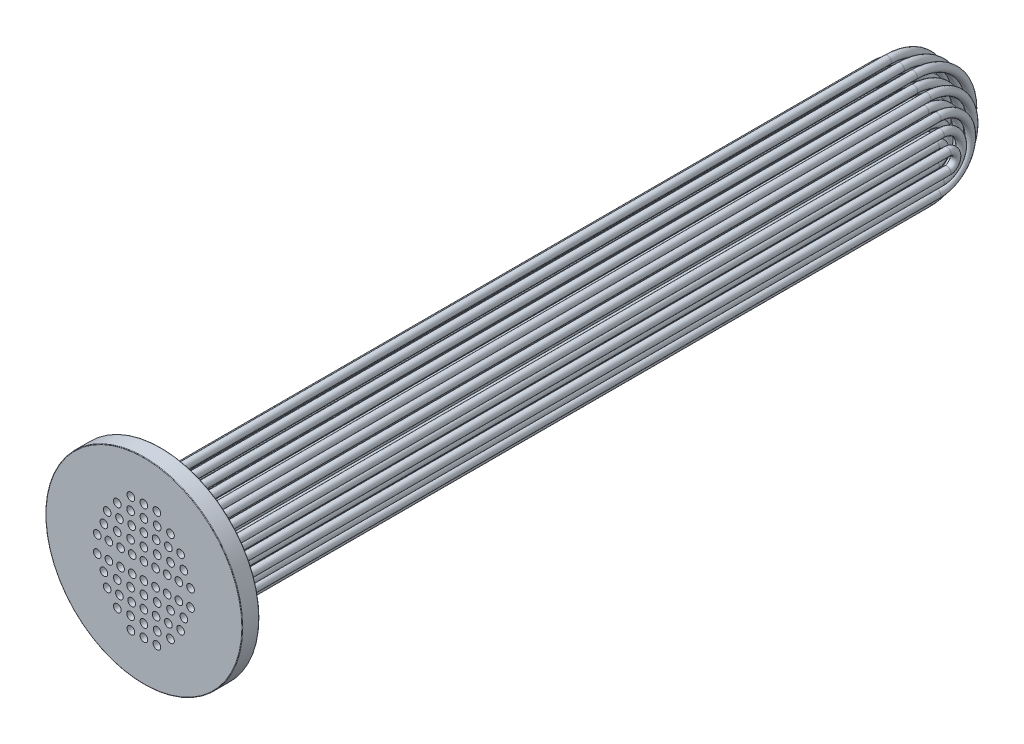
SolidWorks part; units mm, degrees
material "Copper"
ref_plane "Front Plane" through (0, 0, 0) normal (0, 0, 1) x (1, 0, 0)
ref_plane "Top Plane" through (0, 0, 0) normal (0, 1, 0) x (1, 0, 0)
ref_plane "Right Plane" through (0, 0, 0) normal (1, 0, 0) x (0, 0, -1)
ref_axis "Axis1" through (0, 0, -1.27) along (0, 0, 1)
ref_plane "Hub End Plane" through (0, 0, 88.9) normal (0, 0, 1) x (1, 0, 0)
sketch "Sketch1" plane through (0, 0, 0) normal (0, 0, 1) x (1, 0, 0)
  line L0 (0, 314.325) -> (0, 0) construction
  line L1 (41.0276, 311.6359) -> (0, 0) construction
  circle A1 centre (0, 0) radius 295.275
  circle A2 centre (0, 0) radius 314.325 construction
  circle A3 centre (41.0276, 311.6359) radius 17.4625 construction
  dimension "FlangeOD" = 590.55
  dimension "BoltHoleDia" = 34.925
  dimension "BoltCircle" = 628.65
  dimension "HoleOffsetAngle" = 7.5
extrude "Boss-Extrude1" add sketch "Sketch1" along normal blind 50.8
sketch "Sketch7" plane through (0, 0, 0) normal (0, 0, 1) x (1, 0, 0)
  circle A0 centre (0, 0) radius 230.886
  dimension "ID" = 461.772
fillet "Fillet2" radius 1.5875 2 edges at (295.275, 0, 50.8) (295.275, 0, 0)
ref_plane "lug mating plane" through (0, 0, 25.4) normal (0, 0, 1) x (1, 0, 0)
sketch "Sketch8" plane through (0, 0, 50.8) normal (0, 0, 1) x (1, 0, 0)
  line L0 (0, -211.4829) -> (0, 211.4829) construction
  line L1 (-293.6875, 0) -> (293.6875, 0) construction
  line L2 (0, 25) -> (35, 25) construction
  line L3 (0, 25) -> (-35, 25) construction
  line L4 (0, -25) -> (-35, -25) construction
  line L5 (0, -25) -> (35, -25) construction
  circle A1 centre (0, 25) radius 11.5
  circle A2 centre (0, 0) radius 293.6875 construction
  circle A3 centre (35, 25) radius 11.5
  circle A4 centre (70, 25) radius 11.5
  circle A5 centre (105, 25) radius 11.5
  circle A6 centre (140, 25) radius 11.5
  circle A9 centre (-35, 25) radius 11.5
  circle A10 centre (-70, 25) radius 11.5
  circle A11 centre (-105, 25) radius 11.5
  circle A12 centre (-140, 25) radius 11.5
  circle A15 centre (0, 62.2) radius 11.5
  circle A16 centre (0, 99.4) radius 11.5
  circle A17 centre (0, 136.6) radius 11.5
  circle A18 centre (0, 173.8) radius 11.5
  circle A20 centre (40, 62.2) radius 11.5
  circle A21 centre (80, 62.2) radius 11.5
  circle A22 centre (120, 62.2) radius 11.5
  circle A25 centre (-40, 62.2) radius 11.5
  circle A26 centre (-80, 62.2) radius 11.5
  circle A27 centre (-120, 62.2) radius 11.5
  circle A30 centre (36.7, 99.4) radius 11.5
  circle A31 centre (73.4, 99.4) radius 11.5
  circle A32 centre (110.1, 99.4) radius 11.5
  circle A35 centre (-36.7, 99.4) radius 11.5
  circle A36 centre (-73.4, 99.4) radius 11.5
  circle A37 centre (-110.1, 99.4) radius 11.5
  circle A40 centre (39.9, 136.6) radius 11.5
  circle A41 centre (79.8, 136.6) radius 11.5
  circle A44 centre (-39.9, 136.6) radius 11.5
  circle A45 centre (-79.8, 136.6) radius 11.5
  circle A48 centre (39, 173.8) radius 11.5
  circle A61 centre (-140, -25) radius 11.5
  circle A62 centre (-105, -25) radius 11.5
  circle A63 centre (-70, -25) radius 11.5
  circle A64 centre (-35, -25) radius 11.5
  circle A67 centre (140, -25) radius 11.5
  circle A68 centre (105, -25) radius 11.5
  circle A69 centre (70, -25) radius 11.5
  circle A70 centre (35, -25) radius 11.5
  circle A71 centre (0, -25) radius 11.5
  circle A73 centre (-110.1, -99.4) radius 11.5
  circle A74 centre (-73.4, -99.4) radius 11.5
  circle A75 centre (-36.7, -99.4) radius 11.5
  circle A78 centre (110.1, -99.4) radius 11.5
  circle A79 centre (73.4, -99.4) radius 11.5
  circle A80 centre (36.7, -99.4) radius 11.5
  circle A82 centre (-120, -62.2) radius 11.5
  circle A83 centre (-80, -62.2) radius 11.5
  circle A84 centre (-40, -62.2) radius 11.5
  circle A86 centre (120, -62.2) radius 11.5
  circle A87 centre (80, -62.2) radius 11.5
  circle A88 centre (40, -62.2) radius 11.5
  circle A89 centre (0, -99.4) radius 11.5
  circle A90 centre (0, -62.2) radius 11.5
  circle A95 centre (-39, -173.8) radius 11.5
  circle A98 centre (39, -173.8) radius 11.5
  circle A101 centre (-79.8, -136.6) radius 11.5
  circle A102 centre (-39.9, -136.6) radius 11.5
  circle A105 centre (79.8, -136.6) radius 11.5
  circle A106 centre (39.9, -136.6) radius 11.5
  circle A108 centre (0, -173.8) radius 11.5
  circle A109 centre (0, -136.6) radius 11.5
  circle A110 centre (0, 0) radius 173.8 construction
  circle A111 centre (117, 173.8) radius 11.5 [skipped]
  circle A112 centre (159.6, 136.6) radius 11.5 [skipped]
  circle A113 centre (183.5, 99.4) radius 11.5 [skipped]
  circle A114 centre (200, 62.2) radius 11.5 [skipped]
  circle A115 centre (210, 25) radius 11.5 [skipped]
  circle A116 centre (119.7, 136.6) radius 11.5 [skipped]
  circle A117 centre (78, 173.8) radius 11.5 [skipped]
  circle A118 centre (0, 211) radius 11.5 [skipped]
  circle A119 centre (-39, 173.8) radius 11.5
  circle A121 centre (-159.6, 136.6) radius 11.5 [skipped]
  circle A122 centre (-119.7, 136.6) radius 11.5 [skipped]
  circle A123 centre (-183.5, 99.4) radius 11.5 [skipped]
  circle A124 centre (-210, 25) radius 11.5 [skipped]
  circle A125 centre (-200, 62.2) radius 11.5 [skipped]
  circle A126 centre (-146.8, 99.4) radius 11.5 [skipped]
  circle A127 centre (-160, 62.2) radius 11.5 [skipped]
  circle A128 centre (-175, 25) radius 11.5 [skipped]
  circle A129 centre (175, 25) radius 11.5 [skipped]
  circle A130 centre (160, 62.2) radius 11.5 [skipped]
  circle A131 centre (146.8, 99.4) radius 11.5 [skipped]
  dimension "D1" = 23
  dimension "D2" = 7
  dimension "D9" = 4
  dimension "D13" = 347.6
  dimension "D3" = 25
  dimension "D5" = 35
  dimension "D6" = 35
  dimension "D16" = 2
  dimension "D17" = 39
  dimension "D4" = 7
  dimension "D7" = 6
  dimension "D12" = 6
  dimension "D15" = 6
  dimension "D11" = 6
  dimension "D8" = 6
  dimension "D10" = 5
  dimension "D14" = 5
extrude "Cut-Extrude4" cut sketch "Sketch8" against normal blind 552
sketch3d "3DSketch7"
  line L0 (140, 25, 0) -> (140, 25, -2220)
  line L1 (140, 25, 0) -> (140, 25, 50.8) construction
  line L2 (140, -25, 0) -> (140, -25, -2220)
  arc A0 (140, 25, -2220) -> (140, -25, -2220) centre (140, 0, -2220) cw
  point P8 (115, 0, -2220)
  dimension "D1" = 2220
sweep "Sweep7" add path "3DSketch7" circular profile diameter 23 parameters "D3"=23
sketch3d "3DSketch8"
  line L0 (120, 62.2, 0) -> (120, 62.2, 50.8) construction
  line L1 (120, 62.2, 0) -> (120, 62.2, -2220)
  line L2 (120, -62.2, 0) -> (120, -62.2, -2220)
  arc A1 (120, 62.2, -2220) -> (120, -62.2, -2220) centre (120, 0, -2220) cw
  point P8 (57.8, 0, -2220)
  dimension "D1" = 2220
sweep "Sweep8" add path "3DSketch8" circular profile diameter 23 parameters "D3"=23
sketch3d "3DSketch9"
  line L0 (110.1, 99.4, 0) -> (110.1, 99.4, 50.8) construction
  line L1 (110.1, 99.4, 0) -> (110.1, 99.4, -2220)
  line L2 (110.1, -99.4, 0) -> (110.1, -99.4, -2220)
  arc A1 (110.1, 99.4, -2220) -> (110.1, -99.4, -2220) centre (110.1, 0, -2220) cw
  point P8 (10.7, 0, -2220)
  dimension "D1" = 2220
sweep "Sweep9" add path "3DSketch9" circular profile diameter 23 parameters "D3"=23
sketch3d "3DSketch10"
  line L0 (79.8, 136.6, 0) -> (79.8, 136.6, 50.8) construction
  line L1 (79.8, 136.6, 0) -> (79.8, 136.6, -2220)
  line L2 (79.8, -136.6, 0) -> (79.8, -136.6, -2220)
  arc A1 (79.8, 136.6, -2220) -> (79.8, -136.6, -2220) centre (79.8, 0, -2220) cw
  point P8 (-56.8, 0, -2220)
  dimension "D1" = 2220
sweep "Sweep10" add path "3DSketch10" circular profile diameter 23 parameters "D3"=23
sketch3d "3DSketch11"
  line L0 (39, 173.8, 0) -> (39, 173.8, 50.8) construction
  line L1 (39, 173.8, 0) -> (39, 173.8, -2220)
  line L2 (39, -173.8, 0) -> (39, -173.8, -2220)
  arc A1 (39, 173.8, -2220) -> (39, -173.8, -2220) centre (39, 0, -2220) cw
  point P8 (-134.8, 0, -2220)
  dimension "D1" = 2220
sweep "Sweep11" add path "3DSketch11" circular profile diameter 23 parameters "D3"=23
sweep "Cut-Sweep3" cut path "3DSketch7<2>" circular profile diameter 18 parameters "D3"=18
sketch3d "3DSketch7<2>" same geometry as "3DSketch7"
sweep "Cut-Sweep4" cut path "3DSketch8<2>" circular profile diameter 18 parameters "D3"=18
sketch3d "3DSketch8<2>" same geometry as "3DSketch8"
sweep "Cut-Sweep5" cut path "3DSketch9<2>" circular profile diameter 18 parameters "D3"=18
sketch3d "3DSketch9<2>" same geometry as "3DSketch9"
sweep "Cut-Sweep6" cut path "3DSketch10<2>" circular profile diameter 18 parameters "D3"=18
sketch3d "3DSketch10<2>" same geometry as "3DSketch10"
sweep "Cut-Sweep7" cut path "3DSketch11<2>" circular profile diameter 18 parameters "D3"=18
sketch3d "3DSketch11<2>" same geometry as "3DSketch11"
pattern_linear "LPattern12" count 3 spacing 39 along (-1, 0, 0) of bodies 239
pattern_linear "LPattern13" count 5 spacing 39.9 along (-1, 0, 0) of bodies 238
pattern_linear "LPattern14" count 7 spacing 36.7 along (-1, 0, 0) of bodies 237
pattern_linear "LPattern15" count 9 spacing 35 along (-1, 0, 0) of bodies 235
pattern_linear "LPattern16" count 7 spacing 40 along (-1, 0, 0) of bodies 236
ref_plane "Plane1" through (0, 0, -1060) normal (0, 0, 1) x (1, 0, 0)
equation "\"D1@lug mating plane\"=\"FlangeThk@Boss-Extrude1\"/2"
